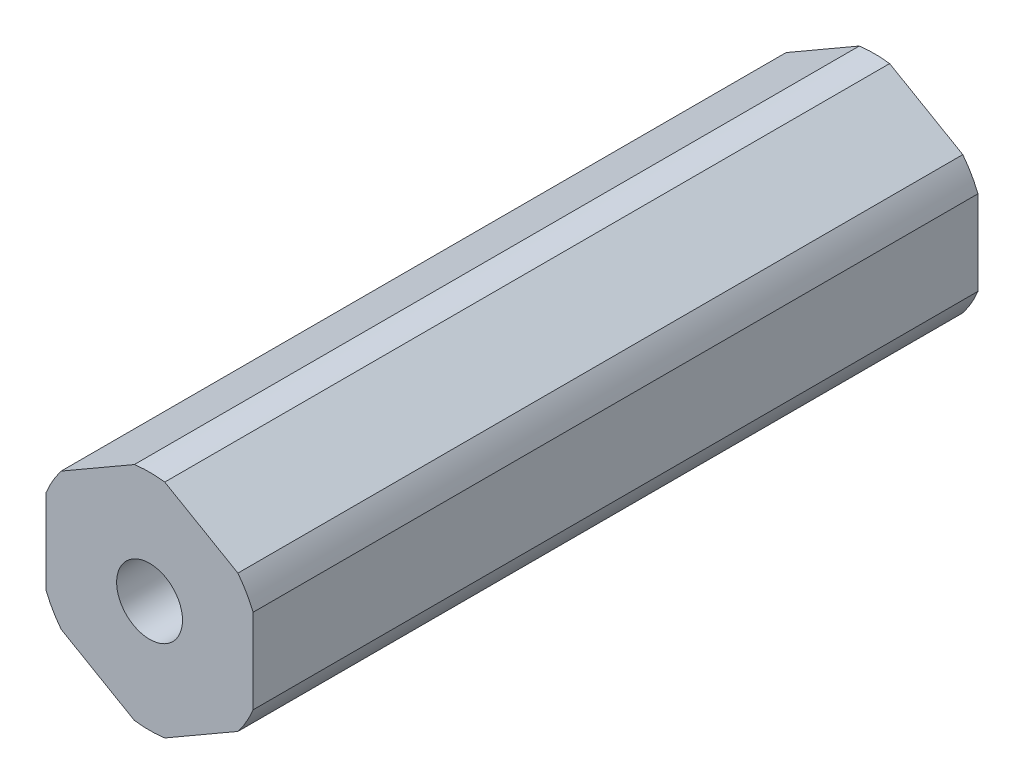
SolidWorks part; units mm, degrees
material "6061-T6 (SS)"
ref_plane "Front Plane" through (0, 0, 0) normal (0, 0, 1) x (1, 0, 0)
ref_plane "Top Plane" through (0, 0, 0) normal (0, 1, 0) x (1, 0, 0)
ref_plane "Right Plane" through (0, 0, 0) normal (1, 0, 0) x (0, 0, -1)
sketch "Sketch1" plane through (0, 0, 0) normal (0, 0, 1) x (1, 0, 0)
  line L1 (0, 7.3323) -> (-6.35, 3.6662)
  line L2 (-6.35, 3.6662) -> (-6.35, -3.6662)
  line L3 (-6.35, -3.6662) -> (0, -7.3323)
  line L4 (0, -7.3323) -> (6.35, -3.6662)
  line L5 (6.35, -3.6662) -> (6.35, 3.6662)
  line L6 (6.35, 3.6662) -> (0, 7.3323)
  circle A0 centre (0, 0) radius 6.858
  circle A1 centre (0, 0) radius 6.35 construction
  dimension "D1" = 12.7
  dimension "D2" = 13.716
extrude "Boss-Extrude1" add sketch "Sketch1" along normal mid plane 44.45 contours L5 A0 L6 L1 L2 L3 L4 region at (0, 0, 0)
sketch "Sketch2" plane through (0, 0, 22.225) normal (0, 0, 1) x (1, 0, 0)
  circle A0 centre (0, 0) radius 2.0193
  dimension "D1" = 4.0386
extrude "Cut-Extrude1" cut sketch "Sketch2" against normal through all
